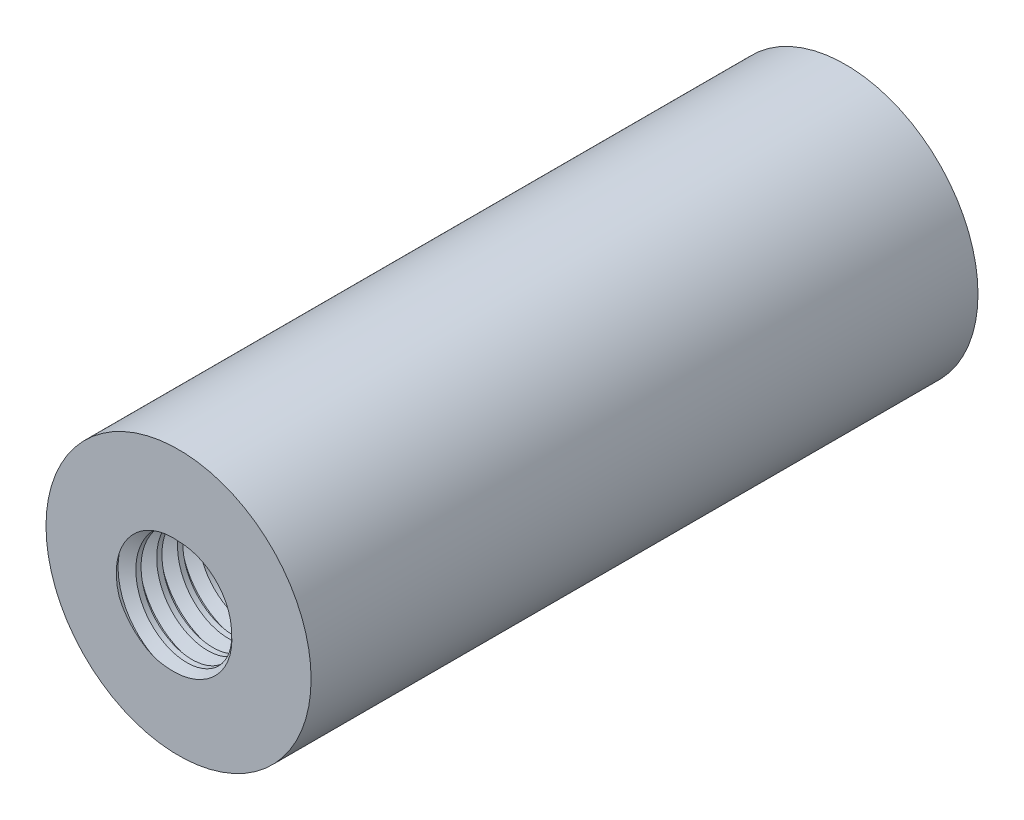
SolidWorks part; units mm, degrees
material "6061-T6 (SS)"
ref_plane "Front Plane" through (0, 0, 0) normal (0, 0, 1) x (1, 0, 0)
ref_plane "Top Plane" through (0, 0, 0) normal (0, 1, 0) x (1, 0, 0)
ref_plane "Right Plane" through (0, 0, 0) normal (1, 0, 0) x (0, 0, -1)
sketch "Sketch1" plane through (0, 0, 0) normal (0, 0, 1) x (1, 0, 0)
  circle A0 centre (0, 0) radius 5.0482
  dimension "D1" = 10.0965
extrude "Boss-Extrude1" add sketch "Sketch1" along normal blind 25.4
sketch "Sketch3" plane through (0, 0, 0) normal (0, 0, -1) x (-1, 0, 0)
  circle A0 centre (0, 0) radius 2.0193
  dimension "D1" = 4.0386
extrude "Cut-Extrude1" cut sketch "Sketch3" against normal through all
thread "Thread1" pitch 0.7937 profile "Thread Profile1" start angle 0, offset 0, length 0, pitch 0.7937, diameter 4.0386
ref_plane "Plane1" through (2.0193, 0, 0) normal (0, -1, 0) x (1, 0, 0)
sketch "Thread Profile1" plane through (2.0193, 0, 0) normal (0, -1, 0) x (1, 0, 0)
  line L0 (0, 0) -> (0, 0.7937) construction
  line L1 (0, 0) -> (0.4296, 0.248)
  line L2 (0.4296, 0.248) -> (0.4296, 0.3473)
  line L3 (0.4296, 0.3473) -> (0, 0.5953)
  line L4 (0.4296, 0.2977) -> (0, 0.2977) construction
  line L11 (0, 0) -> (0, 0.5953)
  point P2 (0, 0)
  dimension "Pitch" = 0.7937
  dimension "Profile_Angle" = 60
  dimension "Profile_Land" = 0.0992
  dimension "Profile_Height" = 0.4296
